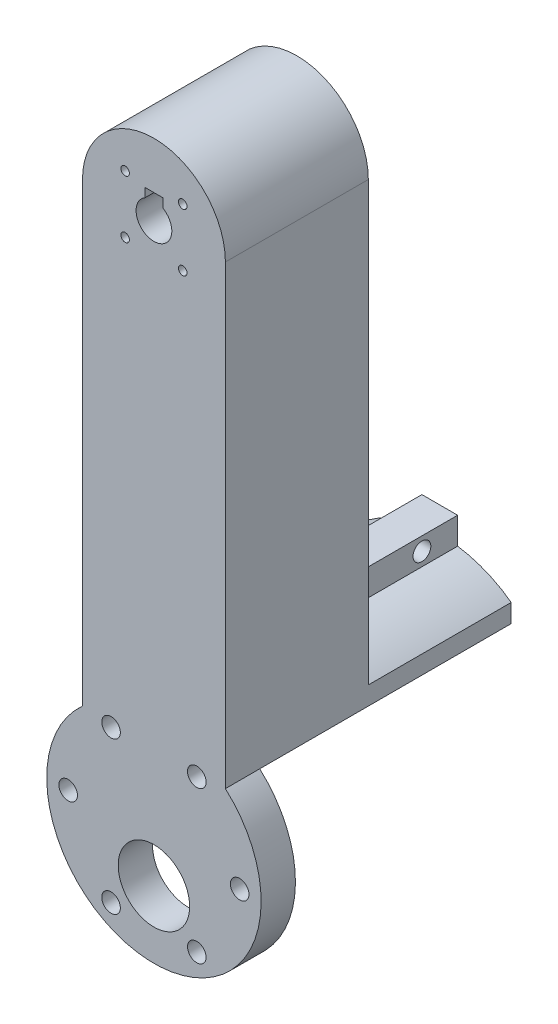
SolidWorks part; units mm, degrees
ref_plane "Front Plane" through (0, 0, 0) normal (0, 0, 1) x (1, 0, 0)
ref_plane "Top Plane" through (0, 0, 0) normal (0, 1, 0) x (1, 0, 0)
ref_plane "Right Plane" through (0, 0, 0) normal (1, 0, 0) x (0, 0, -1)
sketch "Sketch1" plane through (0, 0, 0) normal (0, 0, 1) x (1, 0, 0)
  line L0 (-5.1187, 55.9187) -> (5.1187, 45.6813) construction
  line L2 (12.7, 50.8) -> (12.7, -50.8)
  line L4 (-12.7, 50.8) -> (-12.7, -50.8)
  line L5 (12.7, 50.8) -> (-12.7, -50.8) construction
  line L6 (12.7, -50.8) -> (-12.7, 50.8) construction
  line L7 (5.1187, 55.9187) -> (-5.1187, 45.6813) construction
  line L8 (0, 50.8) -> (0, 51.7208) construction
  arc A0 (-12.7, 50.8) -> (12.7, 50.8) centre (0, 50.8) cw
  arc A1 (12.7, -50.8) -> (-12.7, -50.8) centre (0, -50.8) cw
  circle A2 centre (0, 50.8) radius 3.175
  circle A3 centre (-5.1187, 55.9187) radius 0.762
  circle A4 centre (5.1187, 55.9187) radius 0.762
  circle A5 centre (5.1187, 45.6813) radius 0.762
  circle A6 centre (-5.1187, 45.6813) radius 0.762
  point P0 (0, 0)
  point P14 (0, 50.8)
  point P15 (0, 50.8)
  dimension "D3" = 6.35
  dimension "D6" = 1.524
  dimension "D1" = 25.4
  dimension "D2" = 101.6
  dimension "D4" = 45
  dimension "D5" = 14.478
extrude "Boss-Extrude1" add sketch "Sketch1" along normal blind 25.4
sketch "Sketch2" plane through (0, 0, 0) normal (0, 0, -1) x (-1, 0, 0)
  circle A0 centre (0, -44.45) radius 19.05
  circle A1 centre (0, 50.8) radius 3.175 construction
  arc A2 (-12.7, -50.8) -> (12.7, -50.8) centre (0, -50.8) ccw construction
  circle A3 centre (0, 50.8) radius 3.175
  dimension "D1" = 38.1
extrude "Boss-Extrude2" add sketch "Sketch2" against normal blind 25.4
sketch "Sketch4" plane through (0, 0, 25.4) normal (0, 0, 1) x (1, 0, 0)
  circle A0 centre (0, -44.45) radius 19.05
  arc A1 (-12.7, -30.251) -> (12.7, -30.251) centre (0, -44.45) ccw construction
  dimension "D1" = 38.1
sketch "Sketch3" plane through (0, 0, 25.4) normal (0, 0, 1) x (1, 0, 0)
  line L0 (-15.24, -44.45) -> (15.24, -44.45) construction
  line L1 (15.24, -44.45) -> (7.62, -30.9593) construction
  line L2 (-15.24, -44.45) -> (-7.62, -30.9593) construction
  line L3 (-15.24, -44.45) -> (-7.62, -57.9407) construction
  line L4 (15.24, -44.45) -> (7.62, -57.9407) construction
  line L5 (0, -44.45) -> (0, 0) construction
  circle A0 centre (-7.62, -30.9593) radius 1.651
  circle A1 centre (7.62, -30.9593) radius 1.651
  circle A2 centre (-15.24, -44.45) radius 1.651
  circle A3 centre (-7.62, -57.9407) radius 1.651
  circle A4 centre (7.62, -57.9407) radius 1.651
  circle A5 centre (15.24, -44.45) radius 1.651
  point P10 (0, -44.45)
  dimension "D5" = 3.302
  dimension "D1" = 30.48
  dimension "D2" = 15.494
  dimension "D3" = 30.988
  dimension "D4" = 15.24
extrude "Cut-Extrude1" cut sketch "Sketch3" against normal blind 25.4
sketch "Sketch5" plane through (0, 0, 25.4) normal (0, 0, 1) x (1, 0, 0)
  circle A0 centre (0, -51.562) radius 6.35
  dimension "D1" = 12.7
  dimension "D2" = 7.112
extrude "Cut-Extrude2" cut sketch "Sketch5" against normal blind 25.4
sketch "Sketch6" plane through (0, 0, 0) normal (0, 0, -1) x (-1, 0, 0)
  line L1 (-1.5875, 55.1371) -> (1.5875, 55.1371)
  line L2 (-1.5875, 55.1371) -> (-1.5875, 53.5496)
  line L3 (-1.5875, 53.5496) -> (1.5875, 53.5496)
  line L4 (1.5875, 55.1371) -> (1.5875, 53.5496)
  circle A1 centre (0, 50.8) radius 3.175 construction
  dimension "D1" = 3.175
  dimension "D2" = 1.5875
extrude "Cut-Extrude3" cut sketch "Sketch6" against normal blind 25.4
extrude "Cut-Extrude6" cut sketch "Sketch2<2>" against normal up to surface (25.4 mm away) contours A3 up to face at (0, 54.3434, 25.4)
sketch "Sketch2<2>" plane through (0, 0, 0) normal (0, 0, -1) x (-1, 0, 0) same geometry as "Sketch2"
sketch "Sketch8" plane through (0, 0, 0) normal (0, 0, -1) x (-1, 0, 0)
  circle A0 centre (0, -44.45) radius 19.05
  arc A1 (-1.5875, 53.5496) -> (1.5875, 53.5496) centre (0, 50.8) ccw construction
  arc A2 (-1.5875, 53.5496) -> (1.5875, 53.5496) centre (0, 50.8) ccw
  circle M6 centre (0, -51.562) radius 6.35
  circle M7 centre (7.62, -30.9593) radius 1.651
  circle M8 centre (-15.24, -44.45) radius 1.651
  circle M9 centre (-7.62, -57.9407) radius 1.651
  circle M10 centre (7.62, -57.9407) radius 1.651
  circle M11 centre (15.24, -44.45) radius 1.651
  circle M12 centre (-7.62, -30.9593) radius 1.651
  arc M14 (-12.7, -30.251) -> (12.7, -30.251) centre (0, -44.45) ccw
  dimension "D1" = 38.1
extrude "Cut-Extrude4" cut sketch "Sketch8" against normal blind 19.3 contours A0 M14 M6 M8 M10 M12 M11 M9 M7 | M7 | M12 | M8 | M9 | M6 | M10 | M11 region at (0, -43.5135, 0) region at (0, -51.562, 0) region at (-7.62, -30.9593, 0) region at (15.24, -44.45, 0) region at (7.62, -57.9407, 0) region at (-7.62, -57.9407, 0) region at (-15.24, -44.45, 0) region at (7.62, -30.9593, 0)
sketch "Sketch9" plane through (0, 0, 0) normal (0, 0, -1) x (-1, 0, 0)
  line L0 (12.7, 50.8) -> (12.7, -30.251) construction
  line L1 (-12.7, -30.251) -> (-12.7, 50.8) construction
  line L2 (-12.7, -30.251) -> (-12.7, -26.9904)
  line L3 (12.7, -30.251) -> (12.7, -26.9904)
  arc A0 (-12.7, -30.251) -> (12.7, -30.251) centre (0, -44.45) cw
  arc A1 (-12.7, -26.9904) -> (12.7, -26.9904) centre (0, -44.45) cw
  dimension "D1" = 2.54
extrude "Boss-Extrude3" add sketch "Sketch9" along normal blind 25.4
sketch "Sketch10" plane through (0, 0, 0) normal (0, 0, -1) x (-1, 0, 0)
  line L1 (-3.175, -18.3322) -> (3.175, -18.3322)
  line L2 (-3.175, -18.3322) -> (-3.175, -23.0947)
  line L3 (-3.175, -23.0947) -> (3.175, -23.0947)
  line L4 (3.175, -18.3322) -> (3.175, -23.0947)
  arc A0 (12.7, -26.9904) -> (-12.7, -26.9904) centre (0, -44.45) ccw construction
  point P4 (0, -18.3322)
  dimension "D1" = 6.35
  dimension "D2" = 4.7625
extrude "Boss-Extrude4" add sketch "Sketch10" along normal up to surface (25.4 mm away) up to face at (0, -26.3753, -25.4)
sketch "Sketch11" plane through (3.175, 0, 0) normal (1, 0, 0) x (0, 0, -1)
  line L0 (24.0343, -18.3322) -> (24.0343, -23.0947) construction
  line L1 (25.4, -18.3322) -> (0, -18.3322) construction
  line L2 (25.4, -23.0947) -> (0, -23.0947) construction
  line L3 (0, -26.9904) -> (0, 50.8) construction
  line L4 (25.4, -23.0947) -> (25.4, -18.3322) construction
  circle A0 centre (6.35, -20.7135) radius 1.5875
  circle A1 centre (19.05, -20.7135) radius 1.5875
  point P9 (24.0343, -20.7135)
  dimension "D1" = 3.175
  dimension "D2" = 6.35
  dimension "D3" = 6.35
extrude "Cut-Extrude5" cut sketch "Sketch11" against normal through all
ref_plane "Plane1" through (0, 0, 12.7) normal (0, 0, 1) x (1, 0, 0)
ref_axis "Axis1" through (0, 50.8, 25.4) along (0, 0, -1)
ref_point "Point1"
ref_plane "Plane2" through (0, 0, 37.2197) normal (0, 0, -1) x (-1, 0, 0)
ref_axis "Axis2" through (0, -51.562, 19.3) along (0, 0, 1)
ref_point "wheel orgin point"
